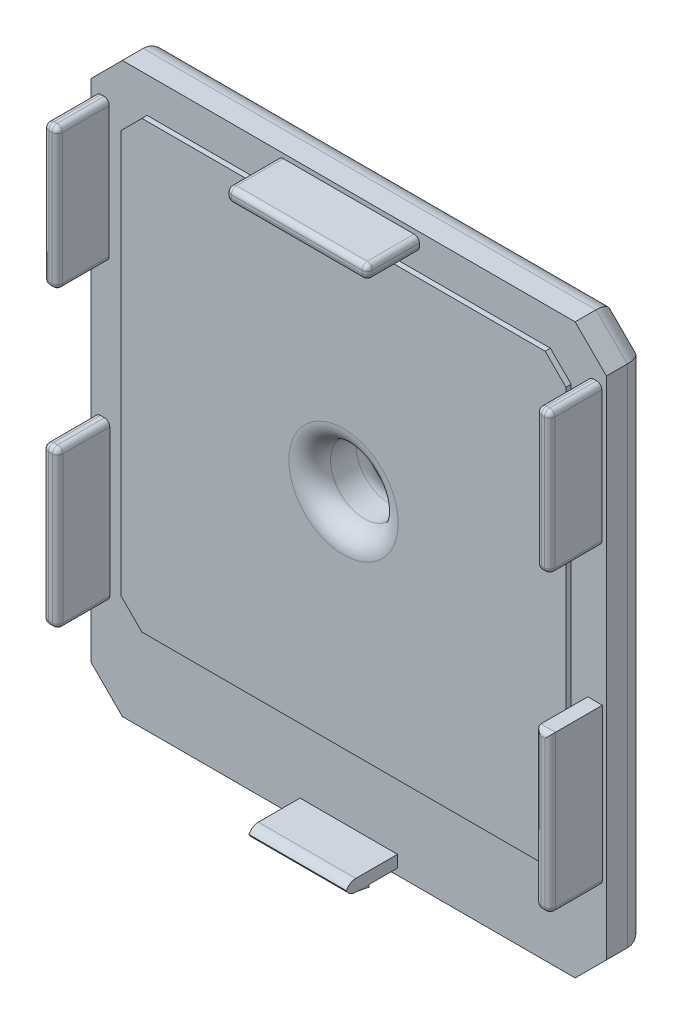
SolidWorks part; units mm, degrees
ref_plane "Plan de face" through (0, 0, 0) normal (0, 0, 1) x (1, 0, 0)
ref_plane "Plan de dessus" through (0, 0, 0) normal (0, 1, 0) x (1, 0, 0)
ref_plane "Plan de droite" through (0, 0, 0) normal (1, 0, 0) x (0, 0, -1)
sketch "Esquisse2" plane through (0, 0, 0) normal (0, 0, 1) x (1, 0, 0)
  line L0 (0, 0) -> (0, 38.7)
  line L1 (0, 38.7) -> (2.0011, 40.7011)
  line L3 (0, 0) -> (2.0011, -2.0011)
  line L5 (42.7022, 0) -> (40.7011, -2.0011)
  line L6 (42.7022, 0) -> (42.7022, 38.7)
  line L7 (42.7022, 38.7) -> (40.7011, 40.7011)
  line L8 (2.0011, 40.7011) -> (40.7011, 40.7011)
  line L9 (2.0011, -2.0011) -> (40.7011, -2.0011)
  dimension "D1" = 38.7
  dimension "D2" = 135
  dimension "D3" = 2.83
  dimension "D4" = 38.7
  dimension "D5" = 38.7
extrude "Boss.-Extru.1" add sketch "Esquisse2" along normal blind 1.5
sketch "Esquisse5" plane through (0, 0, 0) normal (0, 0, -1) x (-1, 0, 0)
  line L0 (-42.7022, 0) -> (-46.0822, 0)
  line L1 (-40.7011, -2.0011) -> (-40.7011, -10.4611)
  line L2 (-46.0822, 0) -> (-46.0822, -10.4611)
  line L3 (-46.0822, -10.4611) -> (-40.7011, -10.4611)
  line L4 (-21.3511, -2.0011) -> (-21.3511, 40.7011)
  line L5 (-2.0011, -2.0011) -> (-40.7011, -2.0011) construction
  line L6 (-40.7011, 40.7011) -> (-2.0011, 40.7011) construction
  line L7 (-21.3511, 44.0811) -> (-21.3511, 40.7011)
  line L8 (3.38, -10.4611) -> (3.38, 44.0811)
  line L9 (-46.0822, -10.4611) -> (3.38, -10.4611)
  line L10 (-46.0822, -10.4611) -> (-46.0822, 44.0811)
  line L11 (-46.0822, 44.0811) -> (3.38, 44.0811)
  line L12 (-21.3511, -10.4611) -> (-21.3511, 44.0811)
  line M9 (-2.0011, -2.0011) -> (0, 0)
  line M10 (0, 0) -> (0, 38.7)
  line M11 (0, 38.7) -> (-2.0011, 40.7011)
  line M12 (-2.0011, 40.7011) -> (-40.7011, 40.7011)
  line M13 (-40.7011, 40.7011) -> (-42.7022, 38.7)
  line M14 (-42.7022, 38.7) -> (-42.7022, 0)
  line M15 (-42.7022, 0) -> (-40.7011, -2.0011)
  line M16 (-40.7011, -2.0011) -> (-2.0011, -2.0011)
extrude "Boss.-Extru.4" add sketch "Esquisse5" along normal blind 3 and the other way blind 1 contours L11 L10 L0 L7 M14 M13 M12 | L12 L9 L8 L11 L7 M12 M11 M10 M9 M16 | L9 L12 L1 M16 | L2 L3 L1 L0 M15 region at (43.4663, -5.3989, 0) region at (44.3922, 0.5054, 0) region at (31.0261, -6.2311, 0) region at (11.6761, -2.6, 0)
sketch "Esquisse6" plane through (0, 0, 1) normal (0, 0, 1) x (1, 0, 0)
  line L0 (21.3511, 44.0811) -> (21.3511, -10.4611)
  line L1 (46.0822, 44.0811) -> (-3.38, 44.0811) construction
  line L2 (46.0822, -10.4611) -> (-3.38, -10.4611) construction
  line L3 (-3.38, -10.4611) -> (-3.38, 44.0811) construction
  line L4 (-3.38, 26.1686) -> (-1.2, 26.1686)
  line L5 (-3.38, 26.1686) -> (-3.38, 40.7086)
  line L6 (-3.38, 40.7086) -> (-1.2, 40.7086)
  line L7 (-1.2, 26.1686) -> (-1.2, 40.7086)
  line L8 (-3.38, 40.7086) -> (5.342, 40.7011)
  line L9 (40.7011, 40.7011) -> (2.0011, 40.7011) construction
  line L10 (-3.38, 40.7086) -> (-1.2, 26.1686)
  line L11 (-1.2, 26.1686) -> (-1.2, 13.9786)
  line L12 (-2.94, 26.6636) -> (-1.64, 26.6636)
  line L13 (-2.94, 26.6636) -> (-2.94, 40.2136)
  line L14 (-2.94, 40.2136) -> (-1.64, 40.2136)
  line L15 (-1.64, 26.6636) -> (-1.64, 40.2136)
  line L16 (-2.94, 26.6636) -> (-1.64, 40.2136) construction
  line L17 (-2.94, 40.2136) -> (-1.64, 26.6636) construction
  line L18 (-3.38, 13.9782) -> (-1.2, -1.9918)
  line L19 (-3.38, 13.9782) -> (-1.2, 13.9782)
  line L20 (-3.38, 13.9782) -> (-3.38, -1.9918)
  line L21 (-3.38, -1.9918) -> (-1.2, -1.9918)
  line L22 (-1.2, 13.9782) -> (-1.2, -1.9918)
  line L23 (45.6922, 13.5182) -> (44.2922, 13.5182)
  line L24 (-2.99, -1.5318) -> (-1.59, -1.5318)
  line L25 (-2.99, -1.5318) -> (-2.99, 13.5182)
  line L26 (-2.99, 13.5182) -> (-1.59, 13.5182)
  line L27 (-1.59, -1.5318) -> (-1.59, 13.5182)
  line L28 (-2.99, -1.5318) -> (-1.59, 13.5182) construction
  line L29 (-2.99, 13.5182) -> (-1.59, -1.5318) construction
  line L30 (28.6211, 44.0811) -> (14.0811, 44.0811)
  line L31 (21.3511, 44.0811) -> (21.3511, 41.9011)
  line L32 (28.6211, 41.9011) -> (14.0811, 41.9011)
  line L33 (14.0811, 44.0811) -> (14.0811, 41.9011)
  line L34 (26.4511, -10.4611) -> (16.2511, -10.4611)
  line L35 (21.3511, -10.4611) -> (21.3511, -8.8411)
  line L36 (26.4511, -8.8411) -> (16.2511, -8.8411)
  line L37 (16.2511, -10.4611) -> (16.2511, -8.8411)
  line L38 (44.2922, -1.5318) -> (44.2922, 13.5182)
  line L39 (45.6922, -1.5318) -> (44.2922, -1.5318)
  line L40 (45.6922, -1.5318) -> (45.6922, 13.5182)
  line L41 (45.6422, 40.2136) -> (44.3422, 40.2136)
  line L42 (44.3422, 26.6636) -> (44.3422, 40.2136)
  line L43 (45.6422, 26.6636) -> (44.3422, 26.6636)
  line L44 (45.6422, 26.6636) -> (45.6422, 40.2136)
  line L45 (28.6211, 44.0811) -> (28.6211, 41.9011)
  line L46 (26.4511, -10.4611) -> (26.4511, -8.8411)
  line L47 (16.2511, -8.8411) -> (26.4511, -10.4611)
  line L48 (14.0811, 44.0811) -> (28.6211, 41.9011)
  line L49 (16.7011, -9.2011) -> (26.0011, -9.2011)
  line L50 (16.7011, -9.2011) -> (16.7011, -10.1011)
  line L51 (16.7011, -10.1011) -> (26.0011, -10.1011)
  line L52 (26.0011, -9.2011) -> (26.0011, -10.1011)
  line L53 (16.7011, -9.2011) -> (26.0011, -10.1011) construction
  line L54 (16.7011, -10.1011) -> (26.0011, -9.2011) construction
  line L56 (14.5761, 43.6411) -> (28.1261, 43.6411)
  line L57 (14.5761, 43.6411) -> (14.5761, 42.3411)
  line L58 (14.5761, 42.3411) -> (28.1261, 42.3411)
  line L59 (28.1261, 43.6411) -> (28.1261, 42.3411)
  line L60 (14.5761, 43.6411) -> (28.1261, 42.3411) construction
  line L61 (14.5761, 42.3411) -> (28.1261, 43.6411) construction
  point P15 (-2.29, 33.4386)
  point P25 (-2.29, 5.9932)
  point P48 (21.3511, -9.6511)
  point P53 (21.3511, 42.9911)
  dimension "D1" = 2.18
  dimension "D2" = 1.3
  dimension "D3" = 13.55
  dimension "D4" = 15.97
  dimension "D5" = 12.19
  dimension "D6" = 2.18
  dimension "D7" = 1.4
  dimension "D8" = 15.05
  dimension "D9" = 2.18
  dimension "D10" = 7.27
extrude "Boss.-Extru.5" add sketch "Esquisse6" along normal blind 5 contours L50 L51 L35 L47 L49 | L49 L47 L35 | L35 L51 L47 | L52 L49 L35 L47 L51 | L24 L27 L18 L25 | L18 L27 L26 L25 | L10 L15 L14 L13 | L12 L15 L10 L13 | L57 L58 L31 L48 L56 | L59 L56 L31 L48 L58 | L31 L58 L48 | L56 L48 L31 | L43 L44 L41 L42 | L40 L23 L38 L39 region at (17.5937, 42.9086, 1) region at (22.7962, 42.5578, 1) region at (23.9242, -9.5972, 1) region at (20.4067, -9.3511, 1) region at (19.906, 43.4244, 1) region at (25.1085, 43.0736, 1) region at (22.2956, -9.9511, 1) region at (18.778, -9.705, 1) region at (-2.4286, 30.5134, 1) region at (-2.1514, 36.3637, 1) region at (-2.131, 9.1733, 1) region at (-2.449, 2.8131, 1) region at (44.9922, 33.4386, 1)
sketch "Esquisse7" plane through (16.7011, 0, 0) normal (-1, 0, 0) x (0, 0, 1)
  line L0 (3.7069, -10.1011) -> (6, -9.6511)
  line L1 (6, -10.1011) -> (1, -10.1011) construction
  line L2 (6, -9.2011) -> (6, -10.1011) construction
  line L3 (6, -9.6511) -> (6, -10.1011)
  line L4 (6, -10.1011) -> (3.7069, -10.1011)
  line L12 (1, -10.1011) -> (3.7069, -10.1011)
  line L13 (1, -10.1011) -> (1, -9.731)
  line L14 (1, -9.731) -> (3.7069, -9.731)
  line L15 (3.7069, -10.1011) -> (3.7069, -9.731)
  line M8 (1, -9.2011) -> (1, -10.1011)
  line M9 (1, -10.1011) -> (6, -10.1011)
  line M10 (6, -10.1011) -> (6, -9.2011)
extrude "Enlèv. mat.-Extru.3" cut sketch "Esquisse7" against normal blind 10 contours L15 L14 M9 M8 | L0 M9 M10 region at (16.7011, -9.9511, 5.2356) region at (16.7011, -9.916, 2.3534)
chamfer "Chanfrein1" distance 3 angle 45 8 edges at (21.3511, -2.0011, 0) (41.7017, -1.0006, 0) (42.7022, 19.35, 0) (41.7017, 39.7006, 0) (21.3511, 40.7011, 0) (1.0006, 39.7006, 0) (0, 19.35, 0) (1.0006, -1.0006, 0)
chamfer "Chanfrein2" distance 3 angle 45 4 edges at (-3.38, 44.0811, -1) (-3.38, -10.4611, -1) (46.0822, -10.4611, -1) (46.0822, 44.0811, -1)
fillet "Congé2" radius 0.5 20 edges at (14.5761, 42.9911, 6) (21.3511, 43.6411, 6) (21.3511, 42.3411, 6) (28.1261, 42.9911, 6) (-2.29, 40.2136, 6) (-2.94, 33.4386, 6) (-1.64, 33.4386, 6) (-2.29, 26.6636, 6) (-2.29, 13.5182, 6) (-2.99, 5.9932, 6) (-1.59, 5.9932, 6) (-2.29, -1.5318, 6) (44.9922, 40.2136, 6) (44.3422, 33.4386, 6) (44.9922, 26.6636, 6) (45.6422, 33.4386, 6) (44.9922, 13.5182, 6) (44.2922, 5.9932, 6) (45.6922, 5.9932, 6) (44.9922, -1.5318, 6)
fillet "Congé3" radius 0.5 38 edges at (27.9797, 42.4876, 5.8536) (27.9797, 43.4947, 5.8536) (14.7226, 42.4876, 5.8536) (14.7226, 43.4947, 5.8536) (-1.7364, -1.3853, 5.8536) (-2.8436, -1.3853, 5.8536) (-1.7364, 13.3718, 5.8536) (-2.8436, 13.3718, 5.8536) (-2.7936, 40.0671, 5.8536) (-1.7864, 40.0671, 5.8536) (-1.7864, 26.81, 5.8536) (-2.7936, 26.81, 5.8536) (44.4887, 40.0671, 5.8536) (45.4958, 40.0671, 5.8536) (45.4958, 26.81, 5.8536) (44.4887, 26.81, 5.8536) (44.4387, -1.3853, 5.8536) (45.5458, -1.3853, 5.8536) (28.1261, 42.3411, 3.25) (28.1261, 43.6411, 3.25) (14.5761, 42.3411, 3.25) (14.5761, 43.6411, 3.25) (21.3511, -9.2011, 6) (21.3511, -9.2011, 1) (-1.59, -1.5318, 3.25) (-2.99, -1.5318, 3.25) (-1.59, 13.5182, 3.25) (-2.99, 13.5182, 3.25) (-2.94, 40.2136, 3.25) (-1.64, 40.2136, 3.25) (-1.64, 26.6636, 3.25) (-2.94, 26.6636, 3.25) (44.3422, 40.2136, 3.25) (45.6422, 40.2136, 3.25) (45.6422, 26.6636, 3.25) (44.3422, 26.6636, 3.25) (44.2922, -1.5318, 3.25) (45.6922, -1.5318, 3.25)
sketch "Esquisse8" plane through (16.7011, 0, 0) normal (-1, 0, 0) x (0, 0, 1)
  line L0 (3.7069, -9.731) -> (3.7069, -10.2951)
  line L1 (3.7069, -10.2951) -> (6.0332, -9.8318)
  line L2 (6.0332, -9.8318) -> (6, -9.6511)
  line L3 (6, -9.6511) -> (3.7069, -9.731)
sketch "Esquisse9" plane through (0, 0, 0) normal (0, 0, -1) x (-1, 0, 0)
  line L0 (-39.5803, 37.5792) -> (-3.1219, 1.1208)
  line L1 (-39.4585, 37.7011) -> (-39.7022, 37.4574) construction
  line L2 (-3.2438, 0.9989) -> (-3, 1.2426) construction
  circle A0 centre (-21.3511, 19.35) radius 12
extrude "Boss.-Extru.7" add sketch "Esquisse9" along normal blind 4.9484 contours L0 A0 | L0 A0 region at (17.7498, 22.9513, 0) region at (24.9524, 15.7487, 0)
sketch "Esquisse13" plane through (0, 0, 1) normal (0, 0, 1) x (1, 0, 0)
  line L1 (16.6736, -9.8563) -> (26.0239, -9.8563)
  line L2 (16.6736, -9.8563) -> (16.6736, -8.7096)
  line L3 (16.6736, -8.7096) -> (26.0239, -8.7096)
  line L4 (26.0239, -9.8563) -> (26.0239, -8.7096)
sketch "Esquisse20" plane through (0, 0, 1.5) normal (0, 0, 1) x (1, 0, 0)
  line L0 (0, 38.7) -> (2.0011, 40.7011)
  line L1 (2.0011, 40.7011) -> (40.7011, 40.7011)
  line L2 (40.7011, 40.7011) -> (42.7022, 38.7)
  line L3 (42.7022, 38.7) -> (42.7022, 0)
  line L4 (42.7022, 0) -> (40.7011, -2.0011)
  line L5 (40.7011, -2.0011) -> (2.0011, -2.0011)
  line L6 (2.0011, -2.0011) -> (0, 0)
  line L7 (0, 0) -> (0, 38.7)
extrude "Boss.-Extru.15" add sketch "Esquisse20" against normal up to surface (4.5 mm away) up to face at (21.3511, 16.81, -3)
sketch "Esquisse22" plane through (0, 0, -4.9484) normal (0, 0, -1) x (-1, 0, 0)
  circle A0 centre (-21.3511, 19.35) radius 3.25
extrude "Enlèv. mat.-Extru.15" cut sketch "Esquisse22" against normal blind 10 contours A0
fillet "Congé14" radius 2 1 edges at (9.3511, 19.35, -4.9484)
fillet "Congé15" radius 2 2 edges at (18.1011, 19.35, 1.5) (18.1011, 19.35, -4.9484)
fillet "Congé16" radius 2 8 edges at (-1.88, 42.5811, -3) (-3.38, 16.81, -3) (-1.88, -8.9611, -3) (21.3511, -10.4611, -3) (44.5822, -8.9611, -3) (46.0822, 16.81, -3) (44.5822, 42.5811, -3) (21.3511, 44.0811, -3)
extrude "Boss.-Extru.16" add sketch "Esquisse13" along normal blind 5
fillet "Congé17" radius 1 2 edges at (21.3488, -8.7096, 6) (21.3488, -9.8563, 6)
